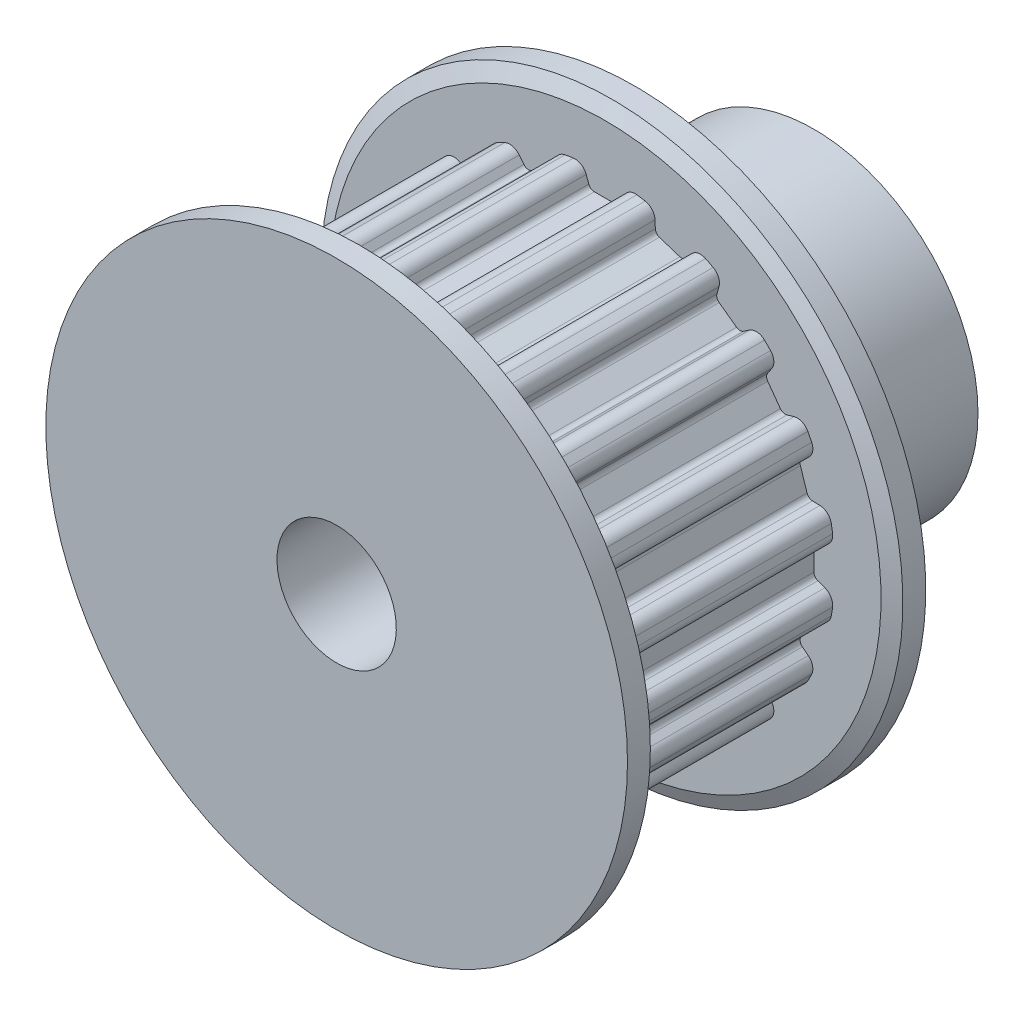
SolidWorks part; units mm, degrees
ref_plane "Front" through (0, 0, 0) normal (0, 0, 1) x (1, 0, 0)
ref_plane "Top" through (0, 0, 0) normal (0, 1, 0) x (1, 0, 0)
ref_plane "Right" through (0, 0, 0) normal (1, 0, 0) x (0, 0, -1)
sketch "support-front-body" plane through (0, 0, 0) normal (0, 0, 1) x (1, 0, 0)
  line L0 (0, 0) -> (0, 7.7) construction
  line L1 (0, 0) -> (0, -7.7) construction
  line L2 (0, 0) -> (7.7, 0) construction
  line L3 (0, 0) -> (-7.7, 0) construction
  circle A0 centre (0, 0) radius 7.7
  dimension "diam-outer" = 15.4
sketch "support-right-body" plane through (0, 0, 0) normal (1, 0, 0) x (0, 0, -1)
  line L0 (0, 0) -> (10, 0) construction
  line L1 (0, 7.7) -> (10, 7.7)
  line L2 (0, 7.7) -> (0, -7.7)
  line L3 (0, -7.7) -> (10, -7.7)
  line L4 (10, 7.7) -> (10, -7.7)
  dimension "length" = 10
sketch "support-right-chamfer" plane through (0, 0, 0) normal (1, 0, 0) x (0, 0, -1)
  line L0 (0, 0) -> (10, 0) construction
  line L1 (0, -7.7) -> (0, -6.7)
  line L2 (0, 7.7) -> (0, -7.7) construction
  line L4 (0, -6.7) -> (1, -7.7)
  line L5 (0, -7.7) -> (10, -7.7) construction
  line L7 (1, -7.7) -> (0, -7.7)
  line L9 (10, -7.7) -> (9, -7.7)
  line L11 (9, -7.7) -> (10, -6.7)
  line L12 (10, 7.7) -> (10, -7.7) construction
  line L14 (10, -6.7) -> (10, -7.7)
  dimension "height-chamfer-front" = 1
  dimension "angle-chamfer-front" = 45
  dimension "angle-chamfer-back" = 45
  dimension "height-chamfer-back" = 1
sketch "support-right-hub" plane through (0, 0, 0) normal (1, 0, 0) x (0, 0, -1)
  line L0 (16, 0) -> (10, 0) construction
  line L1 (10, 5.5) -> (16, 5.5)
  line L2 (10, 5.5) -> (10, -5.5)
  line L3 (10, -5.5) -> (16, -5.5)
  line L4 (16, 5.5) -> (16, -5.5)
  line L6 (0, 0) -> (10, 0) construction
  line L8 (0, 7.7) -> (0, -7.7) construction
  dimension "diam-hub" = 11
  dimension "length-hub" = 6
  dimension "dist-hub" = 10
sketch "support-right-bore" plane through (0, 0, 0) normal (1, 0, 0) x (0, 0, -1)
  line L0 (0, 7.7) -> (0, -7.7) construction
  line L1 (0, 2) -> (16, 2)
  line L2 (0, 2) -> (0, -2)
  line L3 (0, -2) -> (16, -2)
  line L4 (16, 2) -> (16, 0)
  line L5 (16, 0) -> (0, 0) construction
  line L6 (0, 0) -> (10, 0) construction
  line L7 (16, 0) -> (16, -2)
  line L8 (16, -2) -> (16, 2) construction
  dimension "diam-bore" = 4
  dimension "length-bore" = 16
  dimension "angle-bore-bottom" = 180
  dimension "angle-bore" = 90
sketch "support-stop-screw-hole" plane through (0, 0, 0) normal (1, 0, 0) x (0, 0, -1)
  line L1 (6.5667, 11) -> (9.4333, 11)
  line L2 (6.5667, 11) -> (6.5667, -1)
  line L3 (8, -1) -> (9.4333, -1)
  line L4 (9.4333, 11) -> (9.4333, -1)
  line L5 (8, -1) -> (8, 11) construction
  line L6 (8, -1) -> (6.5667, -1)
  line L7 (0, 0) -> (8, 0) construction
  line L8 (0, 7.7) -> (0, -7.7) construction
  dimension "diam-stop-screw-hole" = 2.8665
  dimension "dist-stop-screw-hole" = 8
  dimension "depth-stop-screw-hole" = 12
  dimension "angle-stop-screw-hole" = 180
  dimension "height-stop-screw-hole" = 11
sketch "support-front-keygroove" plane through (0, 0, 0) normal (0, 0, 1) x (1, 0, 0)
  line L0 (0, 0) -> (0, -2) construction
  line L1 (-1, 6) -> (1, 6)
  line L2 (-1, 6) -> (-1, 3.8)
  line L3 (-1, 3.8) -> (1, 3.8)
  line L4 (1, 6) -> (1, 3.8)
  line L5 (0, 0) -> (0, 2) construction
  circle A0 centre (0, 0) radius 2 construction
  dimension "width-keygroove" = 2
  dimension "dist-keygroove" = 8
  dimension "height-keygroove" = 2.2
sketch "support-front-tooth" plane through (0, 0, 0) normal (0, 0, 1) x (1, 0, 0)
  line L0 (0.5479, 7.1316) -> (0.6335, 7.3667)
  line L1 (0, 0) -> (0, 7.7) construction
  line L2 (-0.5479, 7.1316) -> (-0.6335, 7.3667)
  line L3 (-0.36, 7) -> (0.36, 7)
  line L4 (0, 7) -> (-1.0646, 7.626) construction
  line L5 (0, 7) -> (-0.5479, 7.1316) construction
  line L6 (0, 7.7) -> (0.5704, 7.6062) construction
  line L7 (0, 7.7) -> (2.4668, 7.2942) construction
  line L8 (0, 7.626) -> (0, 7) construction
  line L9 (1.0646, 7.626) -> (-1.0646, 7.626) construction
  line L10 (0, 7.626) -> (0, 8.2521) construction
  line L11 (0, 0) -> (1.2334, 7.4971) construction
  line L12 (1.4346, 7.5652) -> (1.6352, 8.1582)
  line L13 (1.6352, 8.1582) -> (3.6522, 7.4761)
  line L14 (3.6522, 7.4761) -> (3.4517, 6.883)
  line L15 (2.5836, 6.5157) -> (2.9601, 6.7755)
  line L16 (2.5836, 6.5157) -> (1.9016, 6.7464)
  line L17 (1.0646, 7.626) -> (1.0646, 8.2521)
  line L21 (-1.0646, 8.2521) -> (-1.0646, 7.626)
  line L22 (1.0646, 8.2521) -> (-1.0646, 8.2521)
  line L23 (1.9016, 6.7464) -> (1.76, 7.1814)
  line L24 (1.4346, 7.5652) -> (1.0646, 7.626) construction
  line L25 (-0.5479, 7.1316) -> (-0.5, 7) construction
  line L26 (-0.5, 7) -> (0.5, 7) construction
  line L27 (0.5, 7) -> (0.5479, 7.1316) construction
  line L28 (0.5704, 7.6062) -> (1.0093, 7.2299) construction
  arc A0 (-0.5479, 7.1316) -> (-0.36, 7) centre (-0.36, 7.2) ccw
  circle A1 centre (0, 0) radius 7.7 construction
  arc A2 (0.6335, 7.3667) -> (1.0646, 7.626) centre (1.0093, 7.2299) cw
  arc A3 (-0.6335, 7.3667) -> (-1.0646, 7.626) centre (-1.0093, 7.2299) ccw
  arc A4 (0.5479, 7.1316) -> (0.36, 7) centre (0.36, 7.2) cw
  circle A5 centre (0, 0) radius 7.7 construction
  arc A6 (1.76, 7.1814) -> (1.4346, 7.5652) centre (1.3601, 7.1722) ccw
  arc A7 (2.9601, 6.7755) -> (3.4517, 6.883) centre (3.2724, 6.5255) cw
  dimension "D3" = 0.4
  dimension "D2" = 40
  dimension "D1" = 0.2
  dimension "D4" = 1
  dimension "height-tooth" = 0.7
  dimension "pitch" = 2.5
sketch "support-right-flange" plane through (0, 0, 0) normal (1, 0, 0) x (0, 0, -1)
  line L0 (0, 4.85) -> (0, 8.1167)
  line L1 (10, 7.7) -> (10, -7.7) construction
  line L2 (0, 8.1167) -> (1, 8.1167) construction
  line L3 (1, 8.1167) -> (1, 9.75)
  line L4 (0, 9.75) -> (1, 9.75)
  line L5 (1, 8.1167) -> (1, 4.85)
  line L6 (1, 4.85) -> (0, 4.85)
  line L7 (5, 7.7) -> (5, 0) construction
  line L8 (0, 7.7) -> (10, 7.7) construction
  line L9 (0, 8.1167) -> (0, 9.75)
  line L10 (9, 4.85) -> (10, 4.85)
  line L11 (9, 8.1167) -> (9, 4.85)
  line L12 (10, 9.75) -> (9, 9.75)
  line L13 (9, 8.1167) -> (9, 9.75)
  line L14 (10, 8.1167) -> (10, 9.75)
  line L15 (10, 4.85) -> (10, 8.1167)
  line L16 (10, 0) -> (0, 0) construction
  line L17 (10, -4.85) -> (10, -8.1167)
  line L18 (10, -8.1167) -> (10, -9.75)
  line L19 (9, -8.1167) -> (9, -9.75)
  line L20 (10, -9.75) -> (9, -9.75)
  line L21 (9, -8.1167) -> (9, -4.85)
  line L22 (9, -4.85) -> (10, -4.85)
  line L23 (1, -4.85) -> (0, -4.85)
  line L24 (1, -8.1167) -> (1, -4.85)
  line L25 (0, -9.75) -> (1, -9.75)
  line L26 (1, -8.1167) -> (1, -9.75)
  line L27 (0, -8.1167) -> (0, -9.75)
  line L28 (0, -4.85) -> (0, -8.1167)
  line L29 (0, 0) -> (10, 0) construction
  line L30 (0, 8.1167) -> (1, 8.1167) construction
  line L31 (0.5, 4.85) -> (0.5, 6.4833) construction
  line L32 (0.5, 6.4833) -> (0.5, 8.1167) construction
  line L33 (0.5, 9.75) -> (0.5, 8.1167) construction
  line L34 (0, 7.7) -> (10, 7.7) construction
  dimension "angle-flange" = 180
  dimension "thickness-flange" = 1
  dimension "diam-flange-inner" = 9.7
  dimension "diam-flange-outer" = 19.5
  dimension "width-flange-inner" = 8
sketch "support-right-flange-profile" plane through (0, 0, 0) normal (1, 0, 0) x (0, 0, -1)
  line L0 (0.7668, 9.75) -> (1, 9.75)
  line L2 (1, 9.75) -> (1, 9.25)
  line L3 (1, 8.1167) -> (1, 4.85) construction
  line L4 (1, 9.25) -> (0.7668, 9.75)
  line L5 (0, 0) -> (10, 0) construction
  line L6 (5, 0) -> (5, 7.7) construction
  line L7 (9, 9.25) -> (9.2332, 9.75)
  line L8 (9, 9.75) -> (9, 9.25)
  line L9 (9.2332, 9.75) -> (9, 9.75)
  dimension "D1" = 25
  dimension "D2" = 0.5
ref_axis "ref-axis-center" through (0, 0, -10) along (0, 0, 1)
ref_plane "ref-plane-front" through (0, 0, 0) normal (0, 0, 1) x (1, 0, 0)
ref_plane "ref-plane-back" through (0, 0, -10) normal (0, 0, 1) x (1, 0, 0)
ref_plane "ref-plane-hub-front" through (0, 0, -10) normal (0, 0, 1) x (1, 0, 0)
ref_plane "ref-plane-hub-back" through (0, 0, -16) normal (0, 0, 1) x (1, 0, 0)
ref_plane "ref-plane-bore-front" through (0, 0, 0) normal (0, 0, 1) x (1, 0, 0)
ref_plane "ref-plane-bore-back" through (0, 0, -16) normal (0, 0, 1) x (1, 0, 0)
ref_plane "ref-plane-stop-screw-hole-top" through (0, 11, 0) normal (0, 1, 0) x (-1, 0, 0)
ref_axis "ref-axis-stop-screw-hole" through (0, 11, -8) along (0, -1, 0)
sketch "Sketch5" plane through (0, 0, 0) normal (1, 0, 0) x (0, 0, -1)
  line L0 (10, 7.7) -> (10, -7.7) construction
  line L1 (0, 7.7) -> (10, 7.7) construction
  line L2 (0, 7.7) -> (0, -7.7) construction
  line L3 (0, 0) -> (10, 0) construction
  line L4 (10, 7.7) -> (10, 0)
  line L5 (0, 7.7) -> (10, 7.7)
  line L6 (0, 7.7) -> (0, 0)
  line L7 (0, 0) -> (10, 0) construction
  line L8 (0, 0) -> (10, 0)
revolve "body" add sketch "Sketch5" angle 360 about L7
sketch "Sketch11" plane through (0, 0, 0) normal (1, 0, 0) x (0, 0, -1)
  line L0 (0, -7.7) -> (0, -6.7) construction
  line L3 (1, -7.7) -> (0, -7.7) construction
  line L5 (0, -6.7) -> (1, -7.7) construction
  line L8 (0, -7.7) -> (0, -6.7)
  line L9 (1, -7.7) -> (0, -7.7)
  line L10 (0, -6.7) -> (1, -7.7)
  line L11 (0, 0) -> (10, 0) construction
  line L12 (0, 0) -> (10, 0) construction
revolve "cut-chamfer-front" [suppressed] cut sketch "Sketch11" angle 360 about L12
sketch "Sketch13" plane through (0, 0, 0) normal (1, 0, 0) x (0, 0, -1)
  line L0 (0, 0) -> (10, 0) construction
  line L1 (10, -7.7) -> (9, -7.7) construction
  line L2 (10, -6.7) -> (10, -7.7) construction
  line L3 (9, -7.7) -> (10, -6.7) construction
  line L4 (0, 0) -> (10, 0) construction
  line L5 (10, -7.7) -> (9, -7.7)
  line L6 (10, -6.7) -> (10, -7.7)
  line L7 (9, -7.7) -> (10, -6.7)
revolve "cut-chamfer-back" [suppressed] cut sketch "Sketch13" angle 360 about L4
sketch "Sketch16" plane through (0, 0, 0) normal (1, 0, 0) x (0, 0, -1)
  line L0 (16, 5.5) -> (16, -5.5) construction
  line L1 (10, 5.5) -> (16, 5.5) construction
  line L2 (16, 0) -> (10, 0) construction
  line L3 (10, 5.5) -> (10, -5.5) construction
  line L4 (16, 5.5) -> (16, 0)
  line L5 (10, 5.5) -> (16, 5.5)
  line L6 (16, 0) -> (10, 0) construction
  line L7 (10, 5.5) -> (10, 0)
  line L8 (16, 0) -> (10, 0)
revolve "body-hub" add sketch "Sketch16" angle 360 about L6
sketch "Sketch17" plane through (0, 0, 0) normal (1, 0, 0) x (0, 0, -1)
  line L0 (16, 2) -> (16, 0) construction
  line L1 (16, 0) -> (0, 0) construction
  line L2 (0, 2) -> (16, 2) construction
  line L3 (0, 2) -> (0, -2) construction
  line L4 (16, 2) -> (16, 0)
  line L5 (16, 0) -> (0, 0) construction
  line L6 (0, 2) -> (16, 2)
  line L7 (0, 2) -> (0, 0)
  line L8 (16, 0) -> (0, 0)
revolve "body-bore" cut sketch "Sketch17" angle 360 about L5
sketch "Sketch19" plane through (0, 0, 0) normal (1, 0, 0) x (0, 0, -1)
  line L0 (6.5667, 11) -> (9.4333, 11) construction
  line L1 (8, -1) -> (8, 11) construction
  line L2 (9.4333, 11) -> (9.4333, -1) construction
  line L3 (8, -1) -> (9.4333, -1) construction
  line L4 (8, 11) -> (9.4333, 11)
  line L5 (8, -1) -> (8, 11) construction
  line L6 (9.4333, 11) -> (9.4333, -1)
  line L7 (8, -1) -> (9.4333, -1)
  line L8 (8, -1) -> (8, 11)
revolve "body-stop-screw-hole" [suppressed] cut sketch "Sketch19" angle 360 about L5
pattern_circular "pattern-stop-screw-hole" [suppressed] count 2 every 90 about axis through (0, 0, -10) along (0, 0, 1) reverse direction yes
sketch "Sketch21" plane through (0, 0, 0) normal (0, 0, 1) x (1, 0, 0)
  line L0 (-1, 6) -> (1, 6) construction
  line L1 (-1, 6) -> (-1, 3.8) construction
  line L2 (-1, 3.8) -> (1, 3.8) construction
  line L3 (1, 6) -> (1, 3.8) construction
  line L4 (-1, 6) -> (1, 6)
  line L5 (-1, 6) -> (-1, 3.8)
  line L6 (-1, 3.8) -> (1, 3.8)
  line L7 (1, 6) -> (1, 3.8)
extrude "cut-keygroove" [suppressed] cut sketch "Sketch21" against normal up to surface (17.5 mm away)
sketch "Sketch23" plane through (0, 0, 0) normal (0, 0, 1) x (1, 0, 0)
  line L0 (0.5479, 7.1316) -> (0.6335, 7.3667) construction
  line L1 (-0.5479, 7.1316) -> (-0.6335, 7.3667) construction
  line L2 (-1.0646, 8.2521) -> (-1.0646, 7.626) construction
  line L3 (1.0646, 8.2521) -> (-1.0646, 8.2521) construction
  line L4 (1.0646, 7.626) -> (1.0646, 8.2521) construction
  line L6 (0.5479, 7.1316) -> (0.6335, 7.3667)
  line L7 (-0.5479, 7.1316) -> (-0.6335, 7.3667)
  line L8 (-1.0646, 8.2521) -> (-1.0646, 7.626)
  line L9 (1.0646, 8.2521) -> (-1.0646, 8.2521)
  line L10 (1.0646, 7.626) -> (1.0646, 8.2521)
  line L11 (-0.36, 7) -> (0.36, 7) construction
  line L12 (-0.36, 7) -> (0.36, 7)
  arc A0 (0.36, 7) -> (0.5479, 7.1316) centre (0.36, 7.2) ccw construction
  arc A1 (-0.5479, 7.1316) -> (-0.36, 7) centre (-0.36, 7.2) ccw construction
  arc A2 (-0.6335, 7.3667) -> (-1.0646, 7.626) centre (-1.0093, 7.2299) ccw construction
  arc A3 (1.0646, 7.626) -> (0.6335, 7.3667) centre (1.0093, 7.2299) ccw construction
  arc A4 (0.36, 7) -> (0.5479, 7.1316) centre (0.36, 7.2) ccw
  arc A5 (-0.5479, 7.1316) -> (-0.36, 7) centre (-0.36, 7.2) ccw
  arc A6 (-0.6335, 7.3667) -> (-1.0646, 7.626) centre (-1.0093, 7.2299) ccw
  arc A7 (1.0646, 7.626) -> (0.6335, 7.3667) centre (1.0093, 7.2299) ccw
extrude "cut-tooth" cut sketch "Sketch23" against normal up to surface (10 mm away) up to plane "ref-plane-back"
pattern_circular "pattern-tooth" count 20 over 360 about axis through (0, 0, -10) along (0, 0, 1) of "cut-tooth"
sketch "Sketch25" plane through (0, 0, 0) normal (1, 0, 0) x (0, 0, -1)
  line L0 (0, 0) -> (10, 0) construction
  line L1 (1, 4.85) -> (0, 4.85) construction
  line L2 (1, 8.1167) -> (1, 4.85) construction
  line L4 (0, 9.75) -> (1, 9.75) construction
  line L5 (0, 8.1167) -> (0, 9.75) construction
  line L6 (0, 4.85) -> (0, 8.1167) construction
  line L7 (0, 0) -> (10, 0) construction
  line L8 (1, 4.85) -> (0, 4.85)
  line L9 (1, 8.1167) -> (1, 4.85)
  line L10 (0, 9.75) -> (1, 9.75)
  line L11 (1, 8.1167) -> (1, 9.75) construction
  line L12 (0, 8.1167) -> (0, 9.75)
  line L13 (0, 4.85) -> (0, 8.1167)
  line L14 (1, 8.1167) -> (1, 9.75)
revolve "body-flange-front" add sketch "Sketch25" angle 360 about L7
sketch "Sketch26" plane through (0, 0, 0) normal (1, 0, 0) x (0, 0, -1)
  line L0 (10, 0) -> (0, 0) construction
  line L1 (9, 4.85) -> (10, 4.85) construction
  line L2 (9, 8.1167) -> (9, 4.85) construction
  line L4 (10, 9.75) -> (9, 9.75) construction
  line L5 (10, 8.1167) -> (10, 9.75) construction
  line L6 (10, 4.85) -> (10, 8.1167) construction
  line L7 (10, 0) -> (0, 0) construction
  line L8 (9, 4.85) -> (10, 4.85)
  line L9 (9, 8.1167) -> (9, 4.85)
  line L10 (10, 9.75) -> (9, 9.75)
  line L11 (9, 8.1167) -> (9, 9.75) construction
  line L12 (10, 8.1167) -> (10, 9.75)
  line L13 (10, 4.85) -> (10, 8.1167)
  line L14 (9, 8.1167) -> (9, 9.75)
revolve "body-flange-back" add sketch "Sketch26" angle 360 about L7
sketch "Sketch28" plane through (0, 0, 0) normal (1, 0, 0) x (0, 0, -1)
  line L0 (1, 9.75) -> (1, 9.25) construction
  line L1 (0.7668, 9.75) -> (1, 9.75) construction
  line L2 (1, 9.25) -> (0.7668, 9.75) construction
  line L3 (1, 9.75) -> (1, 9.25)
  line L4 (0.7668, 9.75) -> (1, 9.75)
  line L5 (1, 9.25) -> (0.7668, 9.75)
  line L6 (10, 0) -> (0, 0) construction
  line L7 (10, 0) -> (0, 0) construction
revolve "body-flange-profile-front" cut sketch "Sketch28" angle 360 about L7
sketch "Sketch29" plane through (0, 0, 0) normal (1, 0, 0) x (0, 0, -1)
  line L0 (10, 0) -> (0, 0) construction
  line L1 (9, 9.75) -> (9, 9.25) construction
  line L2 (9.2332, 9.75) -> (9, 9.75) construction
  line L3 (9, 9.25) -> (9.2332, 9.75) construction
  line L4 (10, 0) -> (0, 0) construction
  line L5 (9, 9.75) -> (9, 9.25)
  line L6 (9.2332, 9.75) -> (9, 9.75)
  line L7 (9, 9.25) -> (9.2332, 9.75)
revolve "body-flange-profile-back" cut sketch "Sketch29" angle 360 about L4
sketch "support-right-cut-body" plane through (0, 0, 0) normal (1, 0, 0) x (0, 0, -1)
  line L0 (10, 7.7) -> (10, -7.7) construction
  line L1 (0, 7.7) -> (10, 7.7) construction
  line L2 (0, 7.7) -> (0, -7.7) construction
  line L3 (0, -7.7) -> (10, -7.7) construction
  line L4 (10, 7.7) -> (10, -7.7) construction
  line L5 (0, 7.7) -> (0, -7.7) construction
  line L6 (0, 7.7) -> (10, 7.7) construction
  line L7 (0, -7.7) -> (10, -7.7) construction
  line L8 (10, 0) -> (0, 0) construction
  line L9 (5, 7.7) -> (5, -7.7) construction
  line L10 (10, 58.5) -> (6.6667, 58.5)
  line L11 (10, 58.5) -> (10, -58.5)
  line L12 (10, -58.5) -> (6.6667, -58.5)
  line L13 (6.6667, 58.5) -> (6.6667, -58.5)
  line L14 (0, 58.5) -> (3.3333, 58.5)
  line L15 (0, 58.5) -> (0, -58.5)
  line L16 (0, -58.5) -> (3.3333, -58.5)
  line L17 (3.3333, 58.5) -> (3.3333, -58.5)
  line L18 (6.6667, 58.5) -> (3.3333, 58.5) construction
  line L19 (3.3333, -58.5) -> (5, -58.5) construction
  line L21 (10, 5.5) -> (6.6667, 5.5)
  line L23 (10, 5.5) -> (16, 5.5) construction
  line L24 (10, -5.5) -> (6.6667, -5.5)
  line L25 (0, 5.5) -> (3.3333, 5.5)
  line L26 (0, -5.5) -> (3.3333, -5.5)
  dimension "diam" = 117
sketch "support-front-cut-body" plane through (0, 0, 0) normal (0, 0, 1) x (1, 0, 0)
  line L0 (58.5, 0) -> (-58.5, 0) construction
  line L1 (0, 58.5) -> (0, 5.5) construction
  line L2 (0, 7.7) -> (0, -7.7) construction
  line L4 (0, 58.5) -> (-54.972, -20.0082) construction
  line L6 (0, -5.5) -> (0, -58.5) construction
  circle A0 centre (0, 32) radius 15.1998
  circle A1 centre (0, 0) radius 58.5 construction
  circle A2 centre (0, 0) radius 5.5 construction
  dimension "D1" = 35
sketch "Sketch31" plane through (0, 0, 0) normal (1, 0, 0) x (0, 0, -1)
  line L0 (0, 58.5) -> (0, -58.5) construction
  line L1 (0, 58.5) -> (3.3333, 58.5) construction
  line L2 (3.3333, 58.5) -> (3.3333, -58.5) construction
  line L3 (10, 58.5) -> (10, -58.5) construction
  line L4 (10, 58.5) -> (6.6667, 58.5) construction
  line L5 (6.6667, 58.5) -> (6.6667, -58.5) construction
  line L7 (0, 58.5) -> (0, 5.5)
  line L8 (0, 58.5) -> (3.3333, 58.5)
  line L9 (3.3333, 58.5) -> (3.3333, 5.5)
  line L10 (10, 58.5) -> (10, 5.5)
  line L11 (10, 58.5) -> (6.6667, 58.5)
  line L12 (6.6667, 58.5) -> (6.6667, 5.5)
  line L13 (10, 5.5) -> (6.6667, 5.5)
  line L14 (10, 5.5) -> (6.6667, 5.5) construction
  line L15 (3.3333, 5.5) -> (0, 5.5)
  line L16 (0, 0) -> (10, 0) construction
  line L17 (10, 0) -> (0, 0) construction
revolve "cut-body" [suppressed] cut sketch "Sketch31" angle 360 about L16
sketch "Sketch33" plane through (0, 0, 0) normal (0, 0, 1) x (1, 0, 0)
  circle A0 centre (0, 32) radius 15.1998 construction
  circle A1 centre (0, 32) radius 15.1998
extrude "cut-front-body" [suppressed] cut sketch "Sketch33" against normal through all
pattern_circular "pattern-cut-front-body" [suppressed] count 6 over 360 about axis through (0, 0, -10) along (0, 0, 1)
